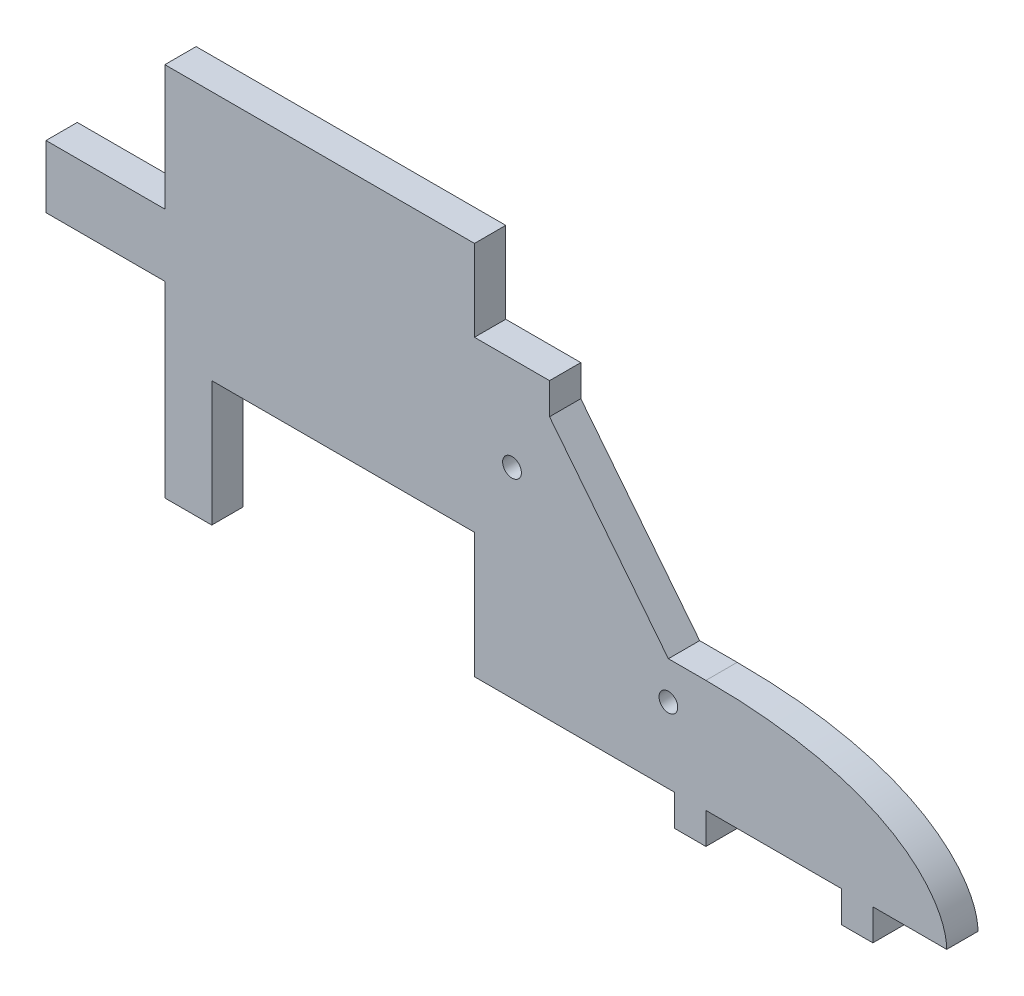
SolidWorks part; units mm, degrees
ref_plane "Plan de face" through (0, 0, 0) normal (0, 0, 1) x (1, 0, 0)
ref_plane "Plan de dessus" through (0, 0, 0) normal (0, 1, 0) x (1, 0, 0)
ref_plane "Plan de droite" through (0, 0, 0) normal (1, 0, 0) x (0, 0, -1)
sketch "Esquisse1" plane through (0, 0, 0) normal (0, 0, 1) x (1, 0, 0)
  line L0 (12, 42) -> (31, 18)
  line L1 (0, 0) -> (32, 0)
  line L2 (0, 0) -> (0, 47)
  line L3 (0, 47) -> (12, 47)
  line L4 (37, 0) -> (37, 18)
  line L6 (12, 47) -> (12, 42)
  line L7 (31, 18) -> (37, 18)
  line L8 (37, 0) -> (37, -5)
  line L9 (37, -5) -> (32, -5)
  line L10 (32, 0) -> (32, -5)
  circle A0 centre (6, 32) radius 1.5
  circle A1 centre (31, 12) radius 1.5
  dimension "D3" = 20
  dimension "D4" = 3
  dimension "D1" = 6
  dimension "D2" = 12
  dimension "D5" = 15
  dimension "D6" = 6
  dimension "D7" = 25
  dimension "D8" = 6
  dimension "D9" = 6
  dimension "D10" = 5
  dimension "D11" = 5
  dimension "D12" = 5
  dimension "D13" = 12
extrude "Boss.-Extru.1" add sketch "Esquisse1" along normal blind 5
sketch "Esquisse2" plane through (0, 0, 0) normal (0, 0, -1) x (-1, 0, 0)
  line L0 (-37, 18) -> (-31, 18) construction
  line L1 (-37, 0) -> (-58.6922, 0)
  line L2 (-37, 0) -> (-37, 18)
  line L3 (-63.6922, 0) -> (-75.5, 0)
  line L4 (42, 0) -> (49.5, 0)
  line L5 (0, 20) -> (0, 60)
  line L6 (0, 60) -> (20, 60)
  line L7 (-10, 167) -> (-1, 167)
  line L8 (0, 0) -> (-32, 0) construction
  line L9 (20, 60) -> (20, 90)
  line L10 (49.5, 120) -> (49.5, 142)
  line L11 (49.5, 0) -> (49.5, 30)
  line L12 (49.5, 30) -> (68.5, 30)
  line L14 (49.5, 40) -> (68.5, 40)
  line L15 (-63.6922, 0) -> (-63.6922, -5)
  line L16 (-63.6922, -5) -> (-58.6922, -5)
  line L17 (-58.6922, 0) -> (-58.6922, -5)
  line L18 (0, 20) -> (42, 20)
  line L19 (68.5, 30) -> (68.5, 40)
  line L20 (49.5, 120) -> (68.5, 120)
  line L21 (49.5, 40) -> (49.5, 110)
  line L22 (0, 47) -> (0, 0) construction
  line L23 (-20, 167) -> (-20, 172)
  line L24 (-20, 172) -> (-10, 172)
  line L25 (-10, 167) -> (-10, 172)
  line L26 (0, 0) -> (-32, 0) construction
  line L27 (42, 20) -> (42, 0)
  line L28 (49.5, 110) -> (68.5, 110)
  line L29 (-37, -5) -> (-37, 18) construction
  line L30 (-1, 167) -> (-1, 142)
  line L31 (20, 90) -> (-25, 90)
  line L32 (-1, 142) -> (49.5, 142)
  line L33 (-20, 167) -> (-25, 167)
  line L34 (-25, 90) -> (-25, 167)
  line L35 (68.5, 120) -> (68.5, 110)
  spline S0 degree 3 poles (-75.5, 0) (-75.5, 5.9822) (-67.6854, 18) (-37, 18) knots 0 0 0 0 1 1 1 1
  dimension "D1" = 38.5
  dimension "D2" = 20
  dimension "D3" = 167
  dimension "D4" = 49.5
  dimension "D5" = 5
  dimension "D6" = 30
  dimension "D7" = 10
  dimension "D8" = 10
  dimension "D9" = 30
  dimension "D10" = 70
  dimension "D11" = 19
  dimension "D12" = 5
  dimension "D13" = 42
  dimension "D14" = 20
  dimension "D15" = 40
  dimension "D16" = 45
  dimension "D17" = 5
  dimension "D19" = 25
  dimension "D21" = 24
extrude "Boss.-Extru.2" add sketch "Esquisse2" against normal blind 5
sketch "Esquisse3" plane through (0, 0, 0) normal (0, 0, -1) x (-1, 0, 0)
  line L0 (20, 60) -> (0, 60) construction
  line L1 (-49.1545, 182.2243) -> (187.1338, 182.2243)
  line L2 (-49.1545, 182.2243) -> (-49.1545, 60)
  line L3 (-49.1545, 60) -> (187.1338, 60)
  line L4 (187.1338, 182.2243) -> (187.1338, 60)
extrude "Enlèv. mat.-Extru.1" cut sketch "Esquisse3" against normal blind 5
